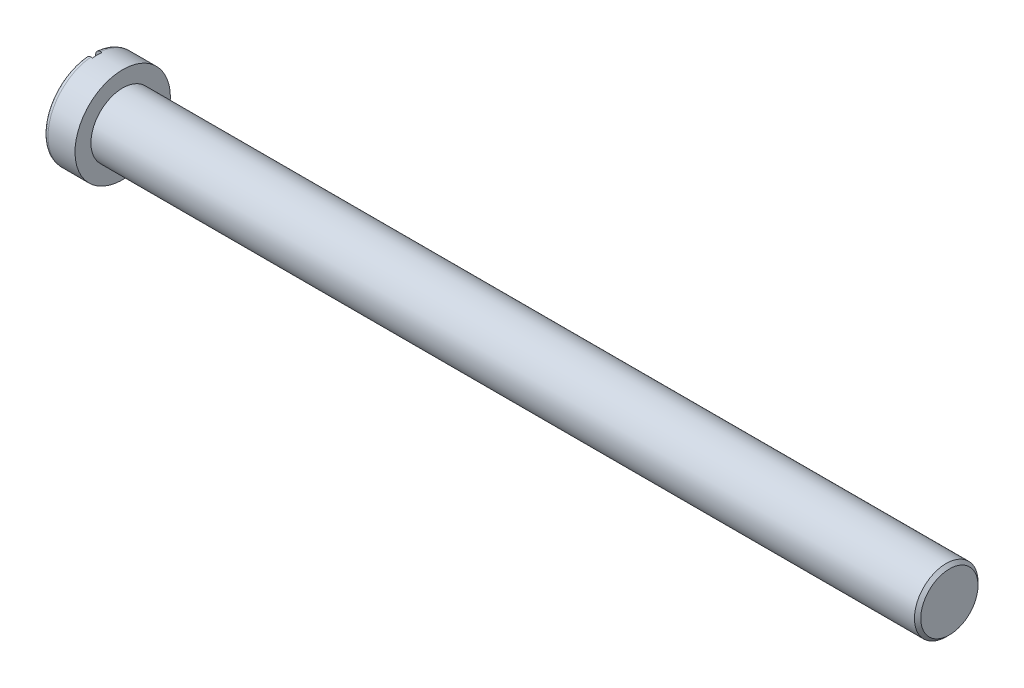
SolidWorks part; units mm, degrees
ref_plane "Front Plane" through (0, 0, 0) normal (0, 0, 1) x (1, 0, 0)
ref_plane "Top Plane" through (0, 0, 0) normal (0, 1, 0) x (1, 0, 0)
ref_plane "Right Plane" through (0, 0, 0) normal (1, 0, 0) x (0, 0, -1)
sketch "Sketch1" plane through (0, 0, 0) normal (1, 0, 0) x (0, 0, -1)
  circle A0 centre (0, 0) radius 10
  circle A1 centre (0, 0) radius 15
  dimension "D1" = 20
  dimension "D2" = 30
extrude "Boss-Extrude1" add sketch "Sketch1" along normal blind 10
extrude "Boss-Extrude2" add sketch "Sketch1<2>" along normal blind 270 contours A0 region at (0, 0, 0)
sketch "Sketch1<2>" plane through (0, 0, 0) normal (1, 0, 0) x (0, 0, -1) same geometry as "Sketch1"
chamfer "Chamfer1" distance 1 angle 45 1 edges at (270, 0, -10)
fillet "Fillet1" radius 1.5 1 edges at (0, 0, -15)
sketch "Sketch2" plane through (0, 0, 0) normal (-1, 0, 0) x (0, 0, 1)
  line L1 (-1.5, 16.2747) -> (1.5, 16.2747)
  line L2 (-1.5, 16.2747) -> (-1.5, -16.2747)
  line L3 (-1.5, -16.2747) -> (1.5, -16.2747)
  line L4 (1.5, 16.2747) -> (1.5, -16.2747)
  line L5 (-1.5, 16.2747) -> (1.5, -16.2747) construction
  line L6 (-1.5, -16.2747) -> (1.5, 16.2747) construction
  point P0 (0, 0)
  dimension "D1" = 3
extrude "Cut-Extrude1" cut sketch "Sketch2" against normal blind 2
